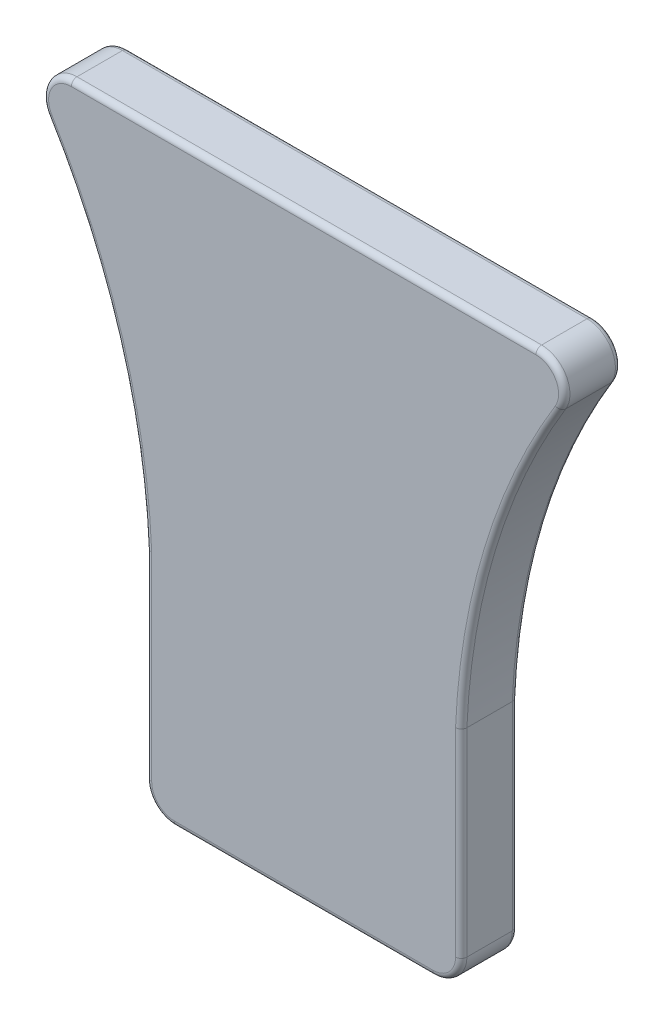
SolidWorks part; units mm, degrees
ref_plane "Front Plane" through (0, 0, 0) normal (0, 0, 1) x (1, 0, 0)
ref_plane "Top Plane" through (0, 0, 0) normal (0, 1, 0) x (1, 0, 0)
ref_plane "Right Plane" through (0, 0, 0) normal (1, 0, 0) x (0, 0, -1)
sketch "Sketch1" plane through (0, 0, 0) normal (0, 0, 1) x (1, 0, 0)
  line L0 (-22.7713, 0) -> (22.7713, 0)
  line L1 (0, 0) -> (0, 105) construction
  line L2 (-40.9393, 105) -> (40.9393, 105)
  line L3 (-27.7713, 5) -> (-27.7713, 40)
  line L4 (27.7713, 5) -> (27.7713, 40)
  line L5 (-22.7713, 5) -> (22.7713, 5) construction
  arc A0 (27.7713, 5) -> (22.7713, 0) centre (22.7713, 5) cw
  arc A1 (-27.7713, 5) -> (-22.7713, 0) centre (-22.7713, 5) ccw
  arc A2 (27.7713, 40) -> (45.2083, 97.397) centre (147.6639, 34.9242) cw
  arc A3 (45.2083, 97.397) -> (40.9393, 105) centre (40.9393, 100) ccw
  arc A4 (-27.7713, 40) -> (-45.2083, 97.397) centre (-147.6639, 34.9242) ccw
  arc A5 (-45.2083, 97.397) -> (-40.9393, 105) centre (-40.9393, 100) cw
  point P17 (0, 0)
  point P19 (0, 0)
  point P20 (105.1863, 105)
  point P23 (72.5066, 105)
  point P24 (0, 0)
  point P25 (0, 0)
  point P26 (0, 0)
  dimension "D2" = 5
  dimension "D4" = 5
  dimension "D5" = 5
  dimension "D6" = 35
extrude "Boss-Extrude1" add sketch "Sketch1" along normal blind 10
fillet "Fillet1" radius 1 10 edges at (32.8454, 69.8056, 0) (45.2991, 102.4479, 0) (-32.8454, 69.8056, 0) (-45.2991, 102.4479, 0) (32.8454, 69.8056, 10) (45.2991, 102.4479, 10) (-32.8454, 69.8056, 10) (-45.2991, 102.4479, 10) (0, 105, 0) (0, 105, 10)
fillet "Fillet2" radius 1 10 edges at (-27.7713, 28.1286, 0) (-26.3069, 1.4645, 0) (27.7713, 28.1286, 0) (26.3069, 1.4645, 0) (-27.7713, 28.1286, 10) (-26.3069, 1.4645, 10) (27.7713, 28.1286, 10) (26.3069, 1.4645, 10) (0, 0, 0) (0, 0, 10)
